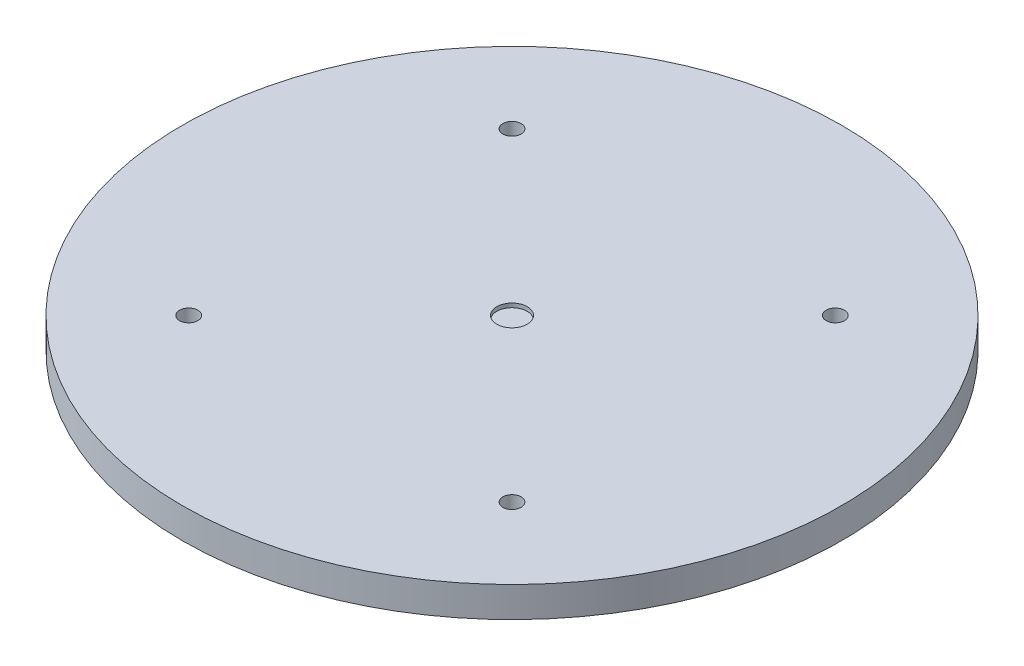
SolidWorks part; units mm, degrees
ref_plane "Front Plane" through (0, 0, 0) normal (0, 0, 1) x (1, 0, 0)
ref_plane "Top Plane" through (0, 0, 0) normal (0, 1, 0) x (1, 0, 0)
ref_plane "Right Plane" through (0, 0, 0) normal (1, 0, 0) x (0, 0, -1)
sketch "Sketch1" plane through (0, 0, 0) normal (0, 1, 0) x (1, 0, 0)
  line L1 (-40.49, -40.49) -> (40.49, -40.49) construction
  line L2 (-40.49, -40.49) -> (-40.49, 40.49) construction
  line L3 (-40.49, 40.49) -> (40.49, 40.49) construction
  line L4 (40.49, -40.49) -> (40.49, 40.49) construction
  line L5 (-40.49, -40.49) -> (40.49, 40.49) construction
  line L6 (-40.49, 40.49) -> (40.49, -40.49) construction
  circle A0 centre (0, 0) radius 82.55
  circle A1 centre (40.49, 40.49) radius 2.286
  circle A2 centre (40.49, -40.49) radius 2.286
  circle A3 centre (-40.49, -40.49) radius 2.286
  circle A4 centre (-40.49, 40.49) radius 2.286
  dimension "D1" = 165.1
  dimension "D3" = 4.572
  dimension "D4" = 4.572
  dimension "D5" = 4.572
  dimension "D6" = 4.572
  dimension "D2" = 80.98
extrude "Boss-Extrude2" add sketch "Sketch1" along normal blind 7.62
sketch "Sketch2" plane through (0, 7.62, 0) normal (0, 1, 0) x (1, 0, 0)
  circle A0 centre (0, 0) radius 3.81
  dimension "D1" = 7.62
extrude "Cut-Extrude1" cut sketch "Sketch2" against normal blind 1.016
